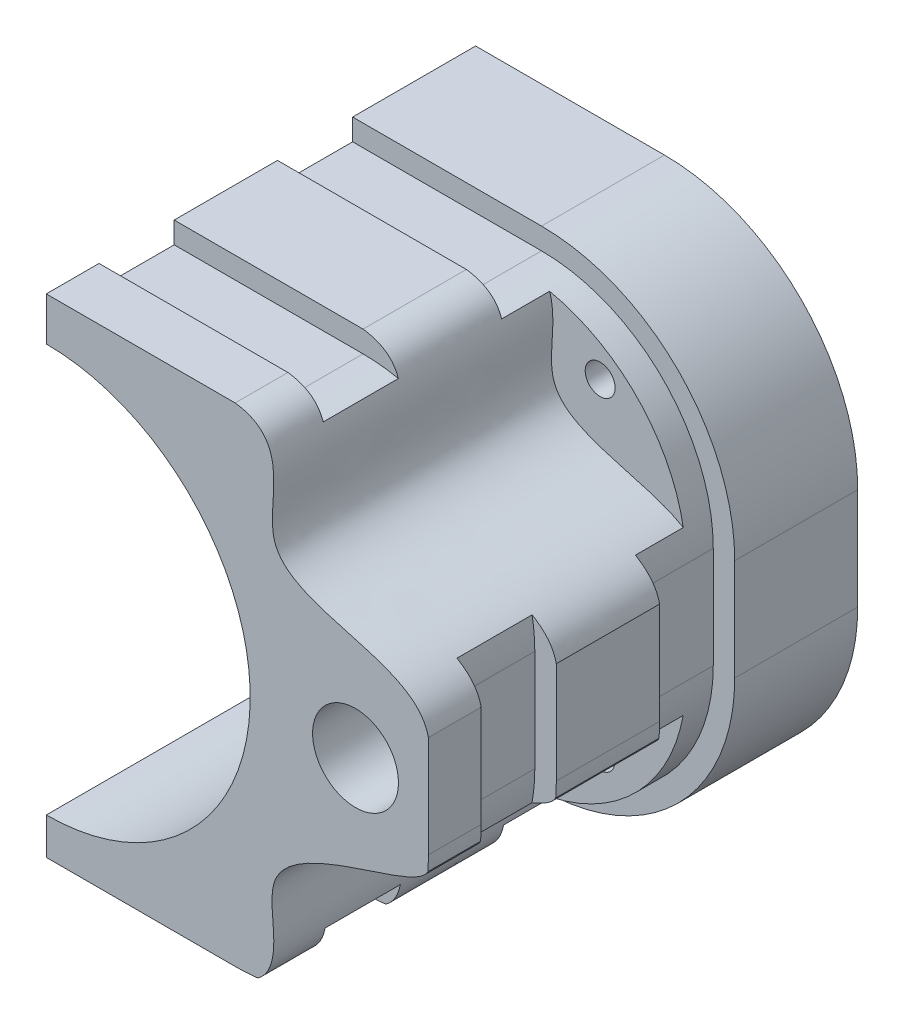
SolidWorks part; units mm, degrees
material "ABS"
ref_plane "Plano frontal" through (0, 0, 0) normal (0, 0, 1) x (1, 0, 0)
ref_plane "Plano superior" through (0, 0, 0) normal (0, 1, 0) x (1, 0, 0)
ref_plane "Plano direito" through (0, 0, 0) normal (1, 0, 0) x (0, 0, -1)
sketch "Esboço1" plane through (0, 0, 0) normal (0, 0, 1) x (1, 0, 0)
  line L2 (-90, -22.4239) -> (-90, -19)
  line L6 (-90, 19) -> (-90, 23.0425)
  line L7 (-90, 23.0425) -> (-72.4018, 23.0425)
  line L8 (-54.4018, 5.0425) -> (-54.4018, -4.4239)
  line L9 (-90, -22.4239) -> (-72.4018, -22.4239)
  arc A0 (-90, -19) -> (-90, 19) centre (-90, 0) ccw
  circle A3 centre (-64.3997, 15.9483) radius 1.3931
  circle A4 centre (-61.1894, 0) radius 4
  arc A5 (-72.4018, 23.0425) -> (-54.4018, 5.0425) centre (-72.4018, 5.0425) cw
  arc A6 (-54.4018, -4.4239) -> (-72.4018, -22.4239) centre (-72.4018, -4.4239) cw
  circle A7 centre (-64.3997, -14.2289) radius 1.3706
  point P1 (-90, 0)
  dimension "D5" = 18
extrude "Ressalto-extrusão1" add sketch "Esboço1" along normal blind 40 contours A0 L6 L7 A5 L8 A6 L9 L2 | A7 | A4 | A3
sketch "Esboço5" plane through (0, 0, 40) normal (0, 0, 1) x (1, 0, 0)
  line L0 (-90.5617, 0) -> (-21.8603, 0) construction
  circle A0 centre (-64.3997, 15.9483) radius 1.3931 construction
  circle A1 centre (-64.3997, -14.2289) radius 1.3706 construction
  arc A2 (-54.4018, 5.0425) -> (-72.4018, 23.0425) centre (-72.4018, 5.0425) ccw construction
  arc A3 (-72.4018, -22.4239) -> (-54.4018, -4.4239) centre (-72.4018, -4.4239) ccw construction
  circle A4 centre (-64.3997, 15.9483) radius 1.3931
  circle A5 centre (-64.3997, -14.2289) radius 1.3706
  arc A6 (-54.4018, 5.0425) -> (-72.4018, 23.0425) centre (-72.4018, 5.0425) ccw
  arc A7 (-70.293, -22.2999) -> (-54.4551, -5.8084) centre (-72.4018, -4.4239) ccw
  spline S0 degree 3 poles (-54.4018, 5.0425) (-55.53, 10.3838) (-70.4539, 8.6368) (-68.3172, 19.152) (-69.4195, 22.6554) (-72.4018, 23.0425) knots 0 0 0 0 0.598412 0.778329 1 1 1 1
  spline S1 degree 3 poles (-54.4551, -5.8084) (-55.0216, -6.906) (-60.8246, -8.6574) (-69.9974, -12.0304) (-68.625, -17.5526) (-68.9475, -20.7122) (-69.6515, -21.8472) (-70.293, -22.2999) knots 0.054308 0.054308 0.054308 0.054308 0.30314 0.598412 0.778329 0.849346 0.932733 0.932733 0.932733 0.932733
  arc M4 (-72.4018, -22.4239) -> (-54.4018, -4.4239) centre (-72.4018, -4.4239) ccw
  arc M6 (-54.4018, 5.0425) -> (-72.4018, 23.0425) centre (-72.4018, 5.0425) ccw
  circle M10 centre (-64.3997, -14.2289) radius 1.3706
  circle M11 centre (-64.3997, 15.9483) radius 1.3931
extrude "Corte-extrusão1" cut sketch "Esboço5" against normal blind 26 contours S0 M6 M11 | S1 M4 M10 | A4 region at (-62.6719, 14.7875, 40) region at (-62.5636, -14.2418, 40)
sketch "Esboço7" plane through (0, 0, 40) normal (0, 0, 1) x (1, 0, 0)
  line L5 (-54.4018, -4.4239) -> (-54.4018, 5.0425)
  line L6 (-72.4018, 23.0425) -> (-90, 23.0425)
  line L7 (-90, 23.0425) -> (-90, 19)
  line L8 (-90, -19) -> (-90, -22.4239)
  line L9 (-90, -22.4239) -> (-72.4018, -22.4239)
  line L10 (-54.4018, -4.4239) -> (-54.4018, 5.0425)
  line L11 (-72.4018, 23.0425) -> (-90, 23.0425)
  line L14 (-90, -22.4239) -> (-72.4018, -22.4239)
  arc A0 (-54.4018, 5.0425) -> (-72.4018, 23.0425) centre (-72.4018, 5.0425) ccw construction
  arc A1 (-70.293, -22.2999) -> (-54.4551, -5.8084) centre (-72.4018, -4.4239) ccw construction
  arc A2 (-54.4018, 5.0425) -> (-72.4018, 23.0425) centre (-72.4018, 5.0425) ccw
  arc A3 (-90, -19) -> (-90, 19) centre (-90, 0) ccw
  arc A4 (-72.4018, -22.4239) -> (-70.293, -22.2999) centre (-72.4018, -4.4239) ccw
  arc A5 (-54.4551, -5.8084) -> (-54.4018, -4.4239) centre (-72.4018, -4.4239) ccw
  arc A6 (-70.293, -22.2999) -> (-54.4551, -5.8084) centre (-72.4018, -4.4239) ccw
  arc A7 (-72.4018, -22.4239) -> (-70.293, -22.2999) centre (-72.4018, -4.4239) ccw
  arc A8 (-54.4551, -5.8084) -> (-54.4018, -4.4239) centre (-72.4018, -4.4239) ccw
  spline S2 degree 3 poles (-874.5966, -567.0331) (102.3374, 71.6396) (-74.3018, -10.3004) (-65.2525, 34.2349) (-102.3028, 38.506) (-909.8497, -523.451) knots -1.800936 -1.800936 -1.800936 -1.800936 0.598412 0.778329 2.434398 2.434398 2.434398 2.434398 only from (-54.4018, 5.0425) to (-72.4018, 23.0425)
  spline S3 degree 3 poles (-930.8651, 487.0271) (-135.4348, -13.3865) (-70.3907, -34.8539) (-68.625, -17.5526) (-69.9974, -12.0304) (-38.4143, -0.4168) (-28.8151, -3.7982) (-1026.723, 228.0125) knots -1.442026 -1.442026 -1.442026 -1.442026 0.137695 0.208712 0.388628 0.6839 2.70161 2.70161 2.70161 2.70161 only from (-70.293, -22.2999) to (-54.4551, -5.8084)
  dimension "D1" = 0
sketch "Esboço8" plane through (-90, 0, 0) normal (-1, 0, 0) x (0, 0, 1)
  line L0 (40, 23.0425) -> (0, 23.0425) construction
  line L1 (28.0838, 23.0425) -> (35.0838, 23.0425)
  line L2 (28.0838, 23.0425) -> (28.0838, 21.0425)
  line L3 (28.0838, 21.0425) -> (35.0838, 21.0425)
  line L4 (35.0838, 23.0425) -> (35.0838, 21.0425)
  line L5 (11.4595, 23.0425) -> (18.4595, 23.0425)
  line L6 (11.4595, 23.0425) -> (11.4595, 21.0425)
  line L7 (11.4595, 21.0425) -> (18.4595, 21.0425)
  line L8 (18.4595, 23.0425) -> (18.4595, 21.0425)
  dimension "D1" = 2
  dimension "D2" = 7
  dimension "D3" = 2
  dimension "D4" = 7
  dimension "D5" = 0
sweep "Varredura de corte1" cut profiles "Esboço8" path "Esboço7"
